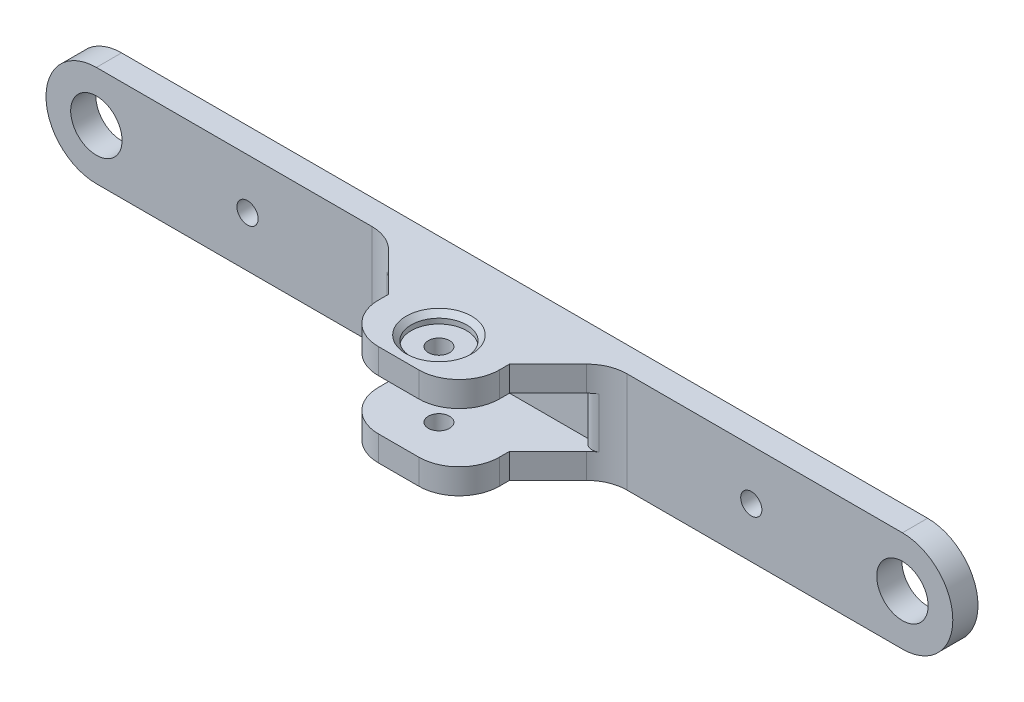
SolidWorks part; units mm, degrees
ref_plane "Plan de face" through (0, 0, 0) normal (0, 0, 1) x (1, 0, 0)
ref_plane "Plan de dessus" through (0, 0, 0) normal (0, 1, 0) x (1, 0, 0)
ref_plane "Plan de droite" through (0, 0, 0) normal (1, 0, 0) x (0, 0, -1)
sketch "Esquisse1" plane through (0, 0, 0) normal (0, 0, 1) x (1, 0, 0)
  line L0 (-80, 0) -> (80, 0) construction
  line L1 (-80, 10) -> (80, 10)
  line L2 (-80, -10) -> (80, -10)
  arc A0 (-80, 10) -> (-80, -10) centre (-80, 0) ccw
  arc A1 (80, -10) -> (80, 10) centre (80, 0) ccw
  point P3 (0, 0)
  dimension "D1" = 160
  dimension "D2" = 20
  dimension "D3" = 80
extrude "Boss.-Extru.1" add sketch "Esquisse1" along normal blind 5
sketch "Esquisse2" plane through (0, 0, 5) normal (0, 0, 1) x (1, 0, 0)
  line L0 (80, 10) -> (-80, 10) construction
  circle A0 centre (-80, 0) radius 5.1
  circle A1 centre (80, 0) radius 5.1
  arc A2 (-80, 10) -> (-80, -10) centre (-80, 0) ccw construction
  arc A3 (80, -10) -> (80, 10) centre (80, 0) ccw construction
  circle A4 centre (-50, 0) radius 2.1
  circle A5 centre (50, 0) radius 2.1
  dimension "D1" = 10.2
  dimension "D2" = 10.2
  dimension "D3" = 4.2
  dimension "D4" = 4.2
  dimension "D5" = 100
  dimension "D6" = 50
  dimension "D7" = 10
  dimension "D8" = 10
extrude "Enlèv. mat.-Extru.1" cut sketch "Esquisse2" against normal through all
sketch "Esquisse3" plane through (0, 0, 5) normal (0, 0, 1) x (1, 0, 0)
  line L0 (80, 10) -> (-80, 10) construction
  line L1 (-12, 10) -> (12, 10)
  line L2 (-12, 10) -> (-12, -10)
  line L3 (-12, -10) -> (12, -10)
  line L4 (12, 10) -> (12, -10)
  line L5 (-80, -10) -> (80, -10) construction
  dimension "D1" = 24
  dimension "D2" = 12
extrude "Boss.-Extru.2" add sketch "Esquisse3" along normal blind 20
chamfer "Chanfrein1" distance 10 angle 45 2 edges
sketch "Esquisse4" plane through (0, 0, 25) normal (0, 0, 1) x (1, 0, 0)
  line L0 (12, 10) -> (-12, 10) construction
  line L1 (-18, 5) -> (18, 5)
  line L2 (-18, 5) -> (-18, -5)
  line L3 (-18, -5) -> (18, -5)
  line L4 (18, 5) -> (18, -5)
  line L5 (-12, 10) -> (-12, -10) construction
  line L6 (12, -10) -> (12, 10) construction
  dimension "D1" = 10
  dimension "D2" = 5
  dimension "D3" = 6
  dimension "D4" = 6
extrude "Enlèv. mat.-Extru.2" cut sketch "Esquisse4" against normal blind 20
sketch "Esquisse5" plane through (0, 10, 0) normal (0, 1, 0) x (1, 0, 0)
  line L0 (12, -25) -> (-12, -25) construction
  line L1 (-12, -25) -> (-12, -15) construction
  circle A0 centre (0, -17) radius 2.1
  dimension "D1" = 4.2
  dimension "D2" = 8
  dimension "D3" = 12
extrude "Enlèv. mat.-Extru.3" cut sketch "Esquisse5" against normal through all
fillet "Congé1" radius 8 6 edges at (-22, 0, 5) (-12, -7.5, 25) (12, -7.5, 25) (22, 0, 5) (-12, 7.5, 25) (12, 7.5, 25)
sketch "Esquisse6" plane through (0, 10, 0) normal (0, 1, 0) x (1, 0, 0)
  circle A0 centre (0, -17) radius 5.5
  dimension "D1" = 11
extrude "Enlèv. mat.-Extru.4" cut sketch "Esquisse6" against normal blind 2
chamfer "Chanfrein2" distance 1 angle 45 1 edges at (0, 10, 22.5)
fillet "Congé4" radius 2 2 edges at (18, 0, 9) (-18, 0, 9)
sketch "Esquisse7" plane through (0, -10, 0) normal (0, -1, 0) x (1, 0, 0)
  circle A0 centre (0, 17) radius 5.5
  dimension "D1" = 11
extrude "Enlèv. mat.-Extru.5" cut sketch "Esquisse7" against normal blind 2
chamfer "Chanfrein3" distance 1 angle 45 1 edges at (0, -10, 11.5)
